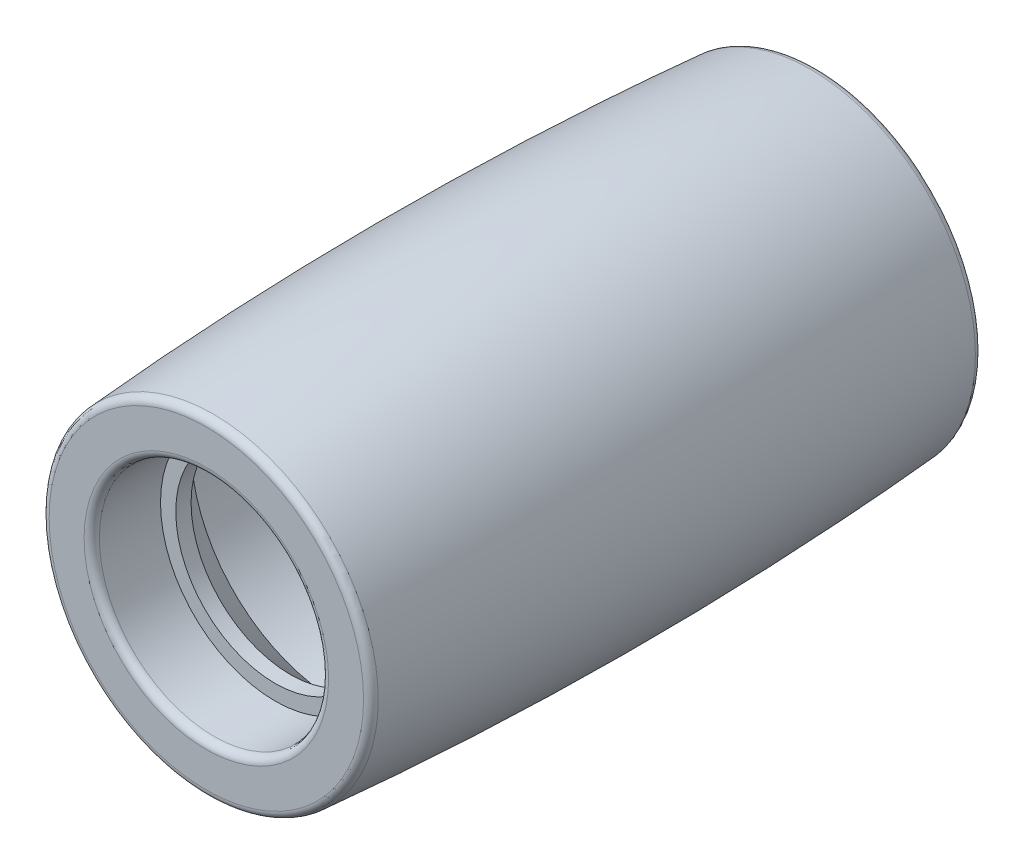
SolidWorks part; units mm, degrees
ref_plane "Ebene vorne" through (0, 0, 0) normal (0, 0, 1) x (1, 0, 0)
ref_plane "Ebene oben" through (0, 0, 0) normal (0, 1, 0) x (1, 0, 0)
ref_plane "Ebene rechts" through (0, 0, 0) normal (1, 0, 0) x (0, 0, -1)
sketch "Skizze1" plane through (0, 0, 0) normal (1, 0, 0) x (0, 0, -1)
  line L27 (0, 0) -> (100, 0) construction
  line L28 (90, 21.5) -> (90, 20.25) construction
  line L29 (85, 19.25) -> (87.1445, 20.25) construction
  line L30 (87.1445, 20.25) -> (90, 20.25) construction
  line L31 (46.3, 19.25) -> (85, 19.25) construction
  line L32 (46.3, 19.25) -> (46.3, 11) construction
  line L33 (46.3, 11) -> (43.3, 11) construction
  line L34 (43.3, 11) -> (43.3, 19.25) construction
  line L35 (21, 19.25) -> (43.3, 19.25) construction
  line L36 (21, 13) -> (28.2121, 20.2121) construction
  line L37 (19, 13) -> (21, 13) construction
  line L38 (19, 15) -> (19, 5) construction
  line L39 (19, 15) -> (10, 15) construction
  line L40 (10, 21.5) -> (10, 15) construction
  line L41 (0, 0) -> (100, 0) construction
  line L42 (90, 21.5) -> (90, 20.25)
  line L43 (85, 19.25) -> (87.1445, 20.25)
  line L44 (87.1445, 20.25) -> (90, 20.25)
  line L45 (46.3, 19.25) -> (85, 19.25)
  line L46 (46.3, 19.25) -> (46.3, 11)
  line L47 (46.3, 11) -> (43.3, 11)
  line L48 (43.3, 11) -> (43.3, 19.25)
  line L49 (27.25, 19.25) -> (43.3, 19.25)
  line L50 (21, 13) -> (27.25, 19.25)
  line L51 (19, 13) -> (21, 13)
  line L52 (19, 15) -> (19, 13)
  line L53 (19, 15) -> (10, 15)
  line L54 (10, 21.5) -> (10, 15)
  arc A2 (90, 21.5) -> (10, 21.5) centre (50, -511.0833) ccw construction
  arc A3 (90, 21.5) -> (10, 21.5) centre (50, -511.0833) ccw
revolve "Rotation1" add sketch "Skizze1" angle 360 about L27
sketch "Skizze4" plane through (0, 0, -43.3) normal (0, 0, 1) x (1, 0, 0)
  circle A0 centre (0, 0) radius 14 construction
  point P4 (0, 14)
hole_wizard "Ø3.6 (3.6) Durchmesser Bohrung2" positions "Skizze4" profile "Skizze5" hole size "Ø3.6" standard "DIN"
sketch "Skizze5" plane through (0, 14, -43.3) normal (1, 0, 0) x (0, -1, 0)
  line L0 (0, 0) -> (0, 10.5815)
  line L1 (0, 10.5815) -> (1.8, 9.5)
  line L2 (1.8, 9.5) -> (1.8, 0)
  line L5 (1.8, 0) -> (0, 0)
  line L10 (0, 10.5815) -> (-1.8, 9.5) construction
  line L11 (0, -6.35) -> (0, 107.95) construction
  dimension "Bohrerdurchmesser" = 3.6
  dimension "Bohrungstiefe" = 9.5
  dimension "Spitzenwinkel" = 118
pattern_circular "Kreismuster2" count 4 over 360 of "Ø3.6 (3.6) Durchmesser Bohrung2"
fillet "Verrundung1" radius 1 3 edges at (21.5, 0, -90) (21.5, 0, -10) (15, 0, -10)
